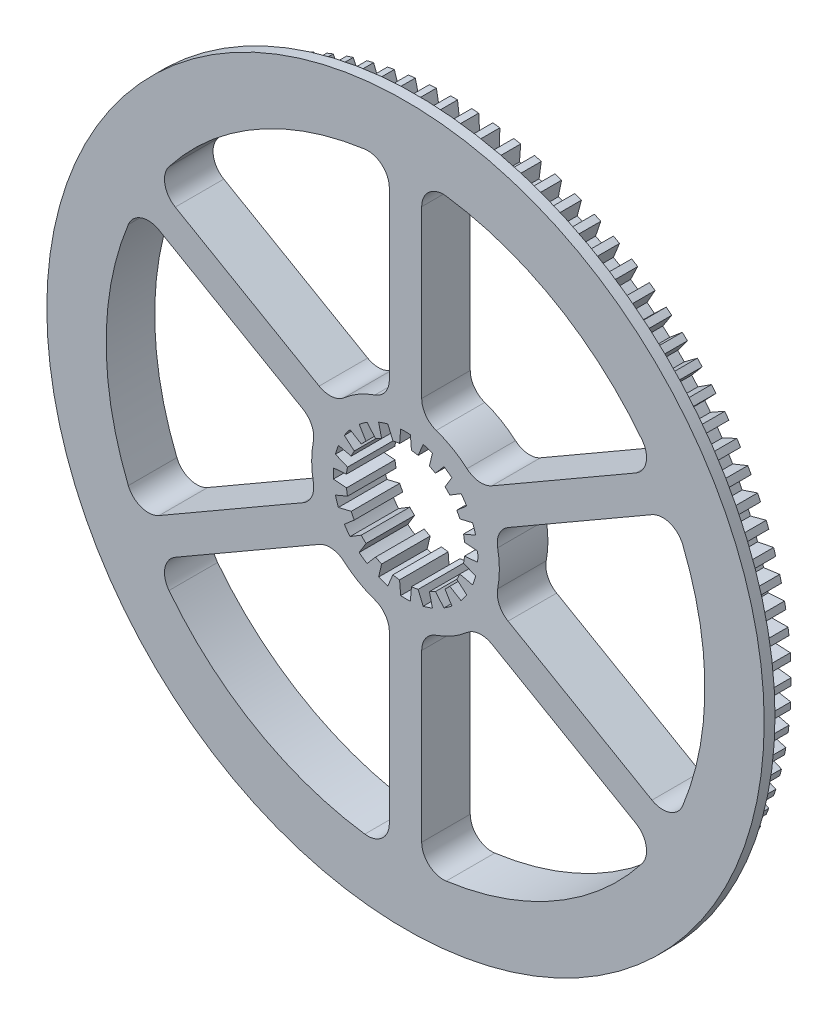
SolidWorks part; units mm, degrees
ref_plane "Plano frontal" through (0, 0, 0) normal (0, 0, 1) x (1, 0, 0)
ref_plane "Plano superior" through (0, 0, 0) normal (0, 1, 0) x (1, 0, 0)
ref_plane "Plano direito" through (0, 0, 0) normal (1, 0, 0) x (0, 0, -1)
sketch "Esboço1" plane through (0, 0, 0) normal (0, 0, 1) x (1, 0, 0)
  line L0 (0, 31.25) -> (0, 13.1363) construction
  line L1 (-0.325, 31.25) -> (-0.325, 13.1363) construction
  line L2 (0.325, 31.25) -> (0.325, 13.1363) construction
  line L3 (-0.5, 31.25) -> (-0.5, 13.1363) construction
  line L4 (0.5, 31.25) -> (0.5, 13.1363) construction
  line L5 (0.325, 31.2483) -> (0.5, 29.7458)
  line L6 (-0.325, 31.2483) -> (-0.5, 29.7458)
  circle A0 centre (0, 0) radius 31.25 construction
  arc A2 (-0.325, 31.2483) -> (0.325, 31.2483) centre (0, 0) cw
  circle A3 centre (0, 0) radius 29.75
  point P7 (0, 31.25)
  point P9 (0, 31.25)
  point P18 (0, 0)
  dimension "D1" = 62.5
  dimension "D3" = 1.5
  dimension "D2" = 0.65
  dimension "D5" = 1
extrude "Ressalto-extrusão1" add sketch "Esboço1" along normal blind 4.5 contours A3 region at (0, 0, 0)
extrude "Ressalto-extrusão2" add sketch "Esboço1<3>" along normal through all contours A3 L5 A2 L6 region at (0, 30.446, 0)
sketch "Esboço1<3>" plane through (0, 0, 0) normal (0, 0, 1) x (1, 0, 0) same geometry as "Esboço1"
pattern_circular "PadrãoCircular1" count 100 over 360 about axis through (0, 0, 4.5) along (0, 0, -1) of "Ressalto-extrusão2" reverse direction yes
sketch "Esboço2" plane through (0, 0, 4.5) normal (0, 0, 1) x (1, 0, 0)
  line L0 (0, 5.9086) -> (0, 3.855) construction
  line L1 (0.45, 3.855) -> (0.45, 5.9086) construction
  line L2 (0.55, 3.855) -> (0.55, 5.9086) construction
  line L3 (-0.45, 3.855) -> (-0.45, 5.9086) construction
  line L4 (-0.55, 3.855) -> (-0.55, 5.9086) construction
  line L5 (0.45, 6.6849) -> (0.55, 5.4724)
  line L6 (-0.45, 6.6849) -> (-0.55, 5.4724)
  arc A0 (-0.55, 5.4724) -> (0.55, 5.4724) centre (0, 0) ccw
  arc A1 (0.45, 6.6849) -> (-0.45, 6.6849) centre (0, 0) ccw
  point P15 (0, 5.9086)
  point P18 (-0.375, 5.6994)
  point P19 (0, 0)
  point P20 (0, 6.7)
  dimension "D4" = 11
  dimension "D1" = 1.1
  dimension "D2" = 0.9
  dimension "D3" = 6.7
extrude "Corte-extrusão1" cut sketch "Esboço2" against normal through all
pattern_circular "PadrãoCircular2" count 20 over 360 about axis through (0, 0, 0) along (0, 0, 1) of "Corte-extrusão1"
sketch "Esboço3" plane through (0, 0, 4.5) normal (0, 0, 1) x (1, 0, 0)
  line L0 (0, 27.75) -> (0, 4.2769) construction
  line L1 (1.5, 8.5697) -> (1.5, 27.7094)
  line L2 (-1.5, 8.5697) -> (-1.5, 27.7094)
  line L3 (8.1716, 2.9858) -> (24.7471, 12.5557)
  line L4 (6.6716, 5.5839) -> (23.2471, 15.1538)
  line L5 (6.6716, -5.5839) -> (23.2471, -15.1538)
  line L6 (8.1716, -2.9858) -> (24.7471, -12.5557)
  line L7 (-1.5, -8.5697) -> (-1.5, -27.7094)
  line L8 (1.5, -8.5697) -> (1.5, -27.7094)
  line L9 (-8.1716, -2.9858) -> (-24.7471, -12.5557)
  line L10 (-6.6716, -5.5839) -> (-23.2471, -15.1538)
  line L11 (-6.6716, 5.5839) -> (-23.2471, 15.1538)
  line L12 (-8.1716, 2.9858) -> (-24.7471, 12.5557)
  circle A0 centre (0, 0) radius 8.7
  circle A1 centre (0, 0) radius 27.75
  circle A2 centre (0, 0) radius 29.75 construction
  arc A3 (5.6727, 3.5652) -> (5.1437, 4.2933) centre (0, 0) ccw construction
  arc A4 (3.7718, 27.4925) -> (1.5, 25.511) centre (3.5, 25.511) ccw
  arc A5 (1.5, 10.1114) -> (2.8458, 8.2214) centre (3.5, 10.1114) ccw
  arc A6 (-1.5, 10.1114) -> (-2.8458, 8.2214) centre (-3.5, 10.1114) cw
  arc A7 (-3.7718, 27.4925) -> (-1.5, 25.511) centre (-3.5, 25.511) cw
  arc A8 (25.6951, 10.4797) -> (22.8432, 11.4565) centre (23.8432, 9.7244) ccw
  arc A9 (21.9233, 17.0127) -> (21.3432, 14.0546) centre (20.3432, 15.7866) cw
  arc A10 (9.5067, 3.7567) -> (8.5428, 1.6462) centre (10.5067, 2.0246) ccw
  arc A11 (8.0067, 6.3547) -> (5.697, 6.5752) centre (7.0067, 8.0868) cw
  arc A12 (21.9233, -17.0127) -> (21.3432, -14.0546) centre (20.3432, -15.7866) ccw
  arc A13 (25.6951, -10.4797) -> (22.8432, -11.4565) centre (23.8432, -9.7244) cw
  arc A14 (8.0067, -6.3547) -> (5.697, -6.5752) centre (7.0067, -8.0868) ccw
  arc A15 (9.5067, -3.7567) -> (8.5428, -1.6462) centre (10.5067, -2.0246) cw
  arc A16 (-3.7718, -27.4925) -> (-1.5, -25.511) centre (-3.5, -25.511) ccw
  arc A17 (3.7718, -27.4925) -> (1.5, -25.511) centre (3.5, -25.511) cw
  arc A18 (-1.5, -10.1114) -> (-2.8458, -8.2214) centre (-3.5, -10.1114) ccw
  arc A19 (1.5, -10.1114) -> (2.8458, -8.2214) centre (3.5, -10.1114) cw
  arc A20 (-25.6951, -10.4797) -> (-22.8432, -11.4565) centre (-23.8432, -9.7244) ccw
  arc A21 (-21.9233, -17.0127) -> (-21.3432, -14.0546) centre (-20.3432, -15.7866) cw
  arc A22 (-9.5067, -3.7567) -> (-8.5428, -1.6462) centre (-10.5067, -2.0246) ccw
  arc A23 (-8.0067, -6.3547) -> (-5.697, -6.5752) centre (-7.0067, -8.0868) cw
  arc A24 (-21.9233, 17.0127) -> (-21.3432, 14.0546) centre (-20.3432, 15.7866) ccw
  arc A25 (-25.6951, 10.4797) -> (-22.8432, 11.4565) centre (-23.8432, 9.7244) cw
  arc A26 (-8.0067, 6.3547) -> (-5.697, 6.5752) centre (-7.0067, 8.0868) ccw
  arc A27 (-9.5067, 3.7567) -> (-8.5428, 1.6462) centre (-10.5067, 2.0246) cw
  point P111 (0, 0)
  dimension "D1" = 2
  dimension "D2" = 2
  dimension "D4" = 2
  dimension "D3" = 3
  dimension "D5" = 6
extrude "Corte-extrusão2" cut sketch "Esboço3" against normal through all both and the other way through all contours L11 A26 A0 A6 L2 A7 A1 A24 | A27 L12 A25 A1 A20 L9 A22 A0 | A11 L4 A9 A1 A4 L1 A5 A0 | A15 L6 A13 A1 A8 L3 A10 A0 | A19 L8 A17 A1 A12 L5 A14 A0 | A23 L10 A21 A1 A16 L7 A18 A0 region at (9.7579, 16.9012, 4.5) region at (-9.7579, 16.9012, 4.5) region at (19.5159, 0, 4.5) region at (-19.5159, 0, 4.5) region at (9.7579, -16.9012, 4.5) region at (-9.7579, -16.9012, 4.5)
sketch "Esboço4" plane through (0, 0, 4.5) normal (0, 0, 1) x (1, 0, 0)
  circle A0 centre (0, 0) radius 27.75
  circle A1 centre (0, 0) radius 33.25
  arc A2 (-3.594, 31.0426) -> (-4.2389, 30.9612) centre (0, 0) ccw construction
  arc A3 (-3.7718, 27.4925) -> (-21.9233, 17.0127) centre (0, 0) ccw construction
  dimension "D1" = 2
extrude "Ressalto-extrusão3" add sketch "Esboço4" against normal blind 1
